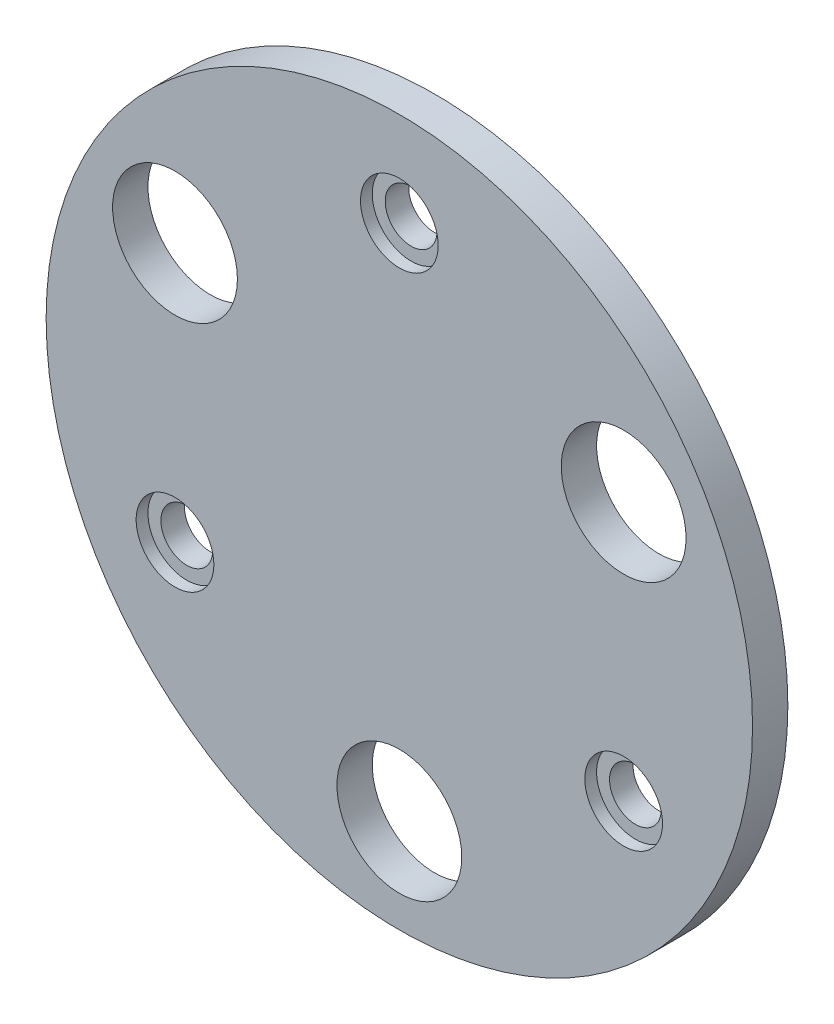
SolidWorks part; units mm, degrees
ref_plane "Front Plane" through (0, 0, 0) normal (0, 0, 1) x (1, 0, 0)
ref_plane "Top Plane" through (0, 0, 0) normal (0, 1, 0) x (1, 0, 0)
ref_plane "Right Plane" through (0, 0, 0) normal (1, 0, 0) x (0, 0, -1)
sketch "Sketch1" plane through (0, 0, 0) normal (0, 0, 1) x (1, 0, 0)
  line L0 (0, 0) -> (0, 15) construction
  line L1 (0, 0) -> (12.9904, 7.5) construction
  circle A0 centre (0, 0) radius 15
  circle A1 centre (9.5263, 5.5) radius 2.65
  circle A2 centre (0, -11) radius 2.65
  circle A3 centre (-9.5263, 5.5) radius 2.65
  circle A4 centre (0, 11) radius 1.1
  circle A5 centre (9.5263, -5.5) radius 1.1
  circle A6 centre (-9.5263, -5.5) radius 1.1
  circle A7 centre (0, 11) radius 1.65
  circle A8 centre (9.5263, -5.5) radius 1.65
  circle A9 centre (-9.5263, -5.5) radius 1.65
  point P14 (0, 0)
  point P20 (0, 0)
  point P26 (0, 0)
  dimension "D1" = 30
  dimension "D4" = 5.3
  dimension "D7" = 2.2
  dimension "D8" = 3
  dimension "D9" = 3.3
  dimension "D2" = 60
  dimension "D3" = 11
  dimension "D6" = 11
  dimension "D5" = 3
  dimension "D10" = 3
extrude "Boss-Extrude1" add sketch "Sketch1" along normal blind 1.5 contours A9 A6 | A7 A4 | A8 A5 | A0 A9 A8 A7 A3 A2 A1 region at (0, 0, 0) region at (-1.6033, 11, 0) region at (7.9229, -5.5, 0) region at (-11.1296, -5.5, 0)
extrude "Cut-Extrude1" cut sketch "Sketch1<5>" against normal blind 0.5 from surface contours A9 A6 | A7 A4 | A8 region at (-1.6033, 11, 0) region at (-11.1296, -5.5, 0) starting at face at (-8.4263, -5.5, 1.5)
sketch "Sketch1<5>" plane through (0, 0, 0) normal (0, 0, 1) x (1, 0, 0) same geometry as "Sketch1"
